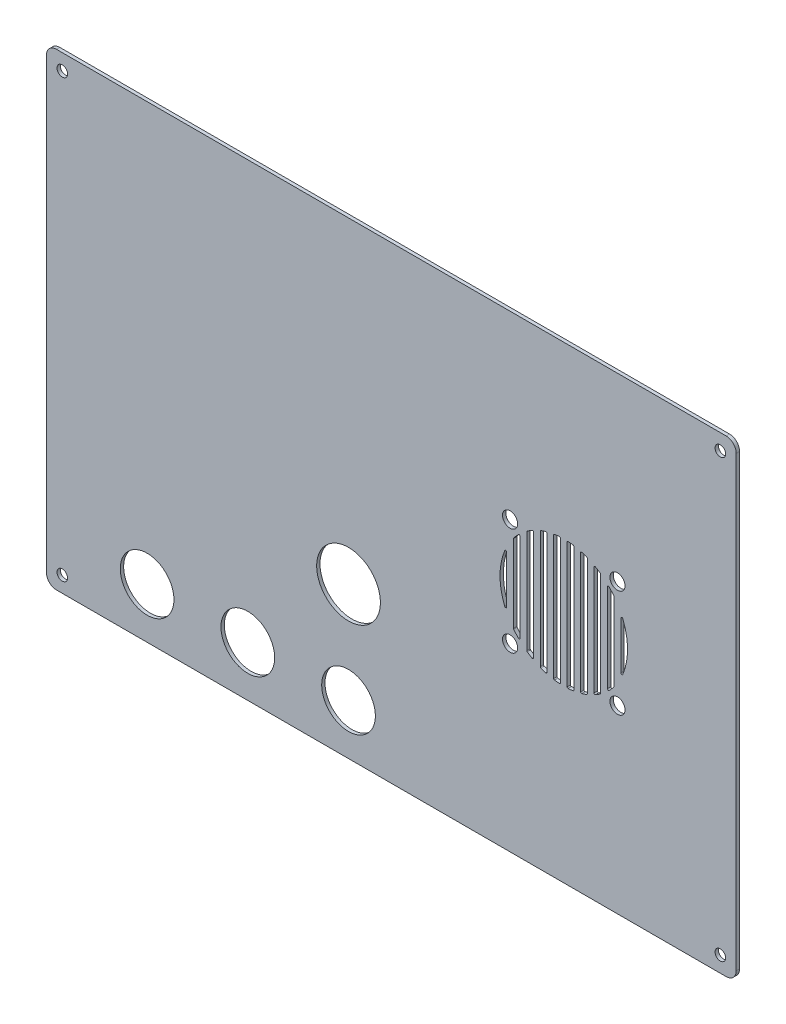
SolidWorks part; units mm, degrees
ref_plane "Спереди" through (0, 0, 0) normal (0, 0, 1) x (1, 0, 0)
ref_plane "Сверху" through (0, 0, 0) normal (0, 1, 0) x (1, 0, 0)
ref_plane "Справа" through (0, 0, 0) normal (1, 0, 0) x (0, 0, -1)
sketch "Эскиз2" plane through (0, 0, 0) normal (0, 0, 1) x (1, 0, 0)
  line L1 (102.75, -69.75) -> (-102.75, -69.75)
  line L2 (102.75, -69.75) -> (102.75, 69.75)
  line L3 (102.75, 69.75) -> (-102.75, 69.75)
  line L4 (-102.75, -69.75) -> (-102.75, 69.75)
  line L5 (102.75, -69.75) -> (-102.75, 69.75) construction
  line L6 (102.75, 69.75) -> (-102.75, -69.75) construction
  point P0 (0, 0)
  dimension "D1" = 205.5
  dimension "D2" = 139.5
base flange "Базовая кромка1" sketch "Эскиз2" thickness 1 reverse thickness direction no parameters "D1"=1.6
fillet "Скругление1" radius 3 4 edges at (-102.75, 69.75, -0.5) (-102.75, -69.75, -0.5) (102.75, -69.75, -0.5) (102.75, 69.75, -0.5)
hole_wizard "Сверло под метчик  спиральное M31" positions "Эскиз4" profile "Эскиз5" hole size "M3x0.5" standard "Ansi Metric"
sketch "Эскиз4" plane through (0, 0, -1) normal (0, 0, -1) x (-1, 0, 0)
  circle A0 centre (-98.0213, -65.0213) radius 1.6 construction
  point P4 (-98.0213, 65.0213)
  point P7 (98.0213, 65.0213)
  point P10 (98.0213, -65.0213)
  point P13 (-98.0213, -65.0213)
sketch "Эскиз5" plane through (98.0213, 65.0213, -1) normal (1, 0, 0) x (0, 1, 0)
  line L0 (0, 0) -> (0, 9.4464)
  line L1 (0, 9.4464) -> (1.575, 8.5)
  line L2 (1.575, 8.5) -> (1.575, 0)
  line L5 (1.575, 0) -> (0, 0)
  line L10 (0, 9.4464) -> (-1.575, 8.5) construction
  line L11 (0, -6.35) -> (0, 107.95) construction
  dimension "Диаметр отверстия" = 3.15
  dimension "Глубина отверстия" = 8.5
  dimension "Угол заточки сверла" = 118
sketch "Эскиз9" plane through (0, 0, -1) normal (0, 0, -1) x (-1, 0, 0)
  line L0 (-102.75, 0) -> (0, 0) construction
  line L1 (-35.375, -16) -> (-67.375, -16) construction
  line L2 (-35.375, -16) -> (-35.375, 16) construction
  line L3 (-35.375, 16) -> (-67.375, 16) construction
  line L4 (-67.375, -16) -> (-67.375, 16) construction
  line L5 (-35.375, -16) -> (-67.375, 16) construction
  line L6 (-35.375, 16) -> (-67.375, -16) construction
  line L7 (-102.75, -66.75) -> (-102.75, 66.75) construction
  circle A0 centre (-51.375, 0) radius 18.5 construction
  circle A1 centre (-67.375, 16) radius 2.25
  circle A2 centre (-35.375, 16) radius 2.25
  circle A3 centre (-35.375, -16) radius 2.25
  circle A4 centre (-67.375, -16) radius 2.25
  point P0 (-51.375, 0)
  point P5 (-51.375, 0)
  dimension "D3" = 4.5
  dimension "D1" = 32
  dimension "D2" = 32
extrude "Вырез-Вытянуть3" cut sketch "Эскиз9" against normal blind 1 normal cut yes
sketch "Эскиз11" plane through (0, 0, -1) normal (0, 0, -1) x (-1, 0, 0)
  line L0 (-68.375, 8.4853) -> (-68.375, -8.4853)
  line L1 (-66.375, 11.6619) -> (-66.375, -11.6619)
  line L2 (-64.375, 13.8564) -> (-64.375, -13.8564)
  line L3 (-52.375, 18.9737) -> (-52.375, -18.9737)
  line L4 (-54.375, 18.7617) -> (-54.375, -18.7617)
  line L5 (-56.375, 18.3303) -> (-56.375, -18.3303)
  line L6 (-58.375, 17.6635) -> (-58.375, -17.6635)
  line L7 (-60.375, 16.7332) -> (-60.375, -16.7332)
  line L8 (-62.375, 15.4919) -> (-62.375, -15.4919)
  line L10 (-51.375, 0) -> (-51.375, 26.4323) construction
  line L11 (-40.375, 15.4919) -> (-40.375, -15.4919)
  line L12 (-42.375, 16.7332) -> (-42.375, -16.7332)
  line L13 (-44.375, 17.6635) -> (-44.375, -17.6635)
  line L14 (-46.375, 18.3303) -> (-46.375, -18.3303)
  line L15 (-48.375, 18.7617) -> (-48.375, -18.7617)
  line L16 (-50.375, 18.9737) -> (-50.375, -18.9737)
  line L17 (-38.375, 13.8564) -> (-38.375, -13.8564)
  line L18 (-36.375, 11.6619) -> (-36.375, -11.6619)
  line L19 (-34.375, 8.4853) -> (-34.375, -8.4853)
  arc A0 (-68.375, 8.4853) -> (-68.375, -8.4853) centre (-51.375, 0) ccw
  arc A1 (-64.375, 13.8564) -> (-66.375, 11.6619) centre (-51.375, 0) ccw
  arc A2 (-60.375, 16.7332) -> (-62.375, 15.4919) centre (-51.375, 0) ccw
  arc A3 (-56.375, 18.3303) -> (-58.375, 17.6635) centre (-51.375, 0) ccw
  arc A4 (-52.375, 18.9737) -> (-54.375, 18.7617) centre (-51.375, 0) ccw
  arc A5 (-66.375, -11.6619) -> (-64.375, -13.8564) centre (-51.375, 0) ccw
  arc A6 (-62.375, -15.4919) -> (-60.375, -16.7332) centre (-51.375, 0) ccw
  arc A7 (-58.375, -17.6635) -> (-56.375, -18.3303) centre (-51.375, 0) ccw
  arc A8 (-54.375, -18.7617) -> (-52.375, -18.9737) centre (-51.375, 0) ccw
  arc A9 (-50.375, -18.9737) -> (-50.375, 18.9737) centre (-51.375, 0) ccw construction
  arc A10 (-48.375, -18.7617) -> (-50.375, -18.9737) centre (-51.375, 0) cw
  arc A11 (-44.375, -17.6635) -> (-46.375, -18.3303) centre (-51.375, 0) cw
  arc A12 (-40.375, -15.4919) -> (-42.375, -16.7332) centre (-51.375, 0) cw
  arc A13 (-36.375, -11.6619) -> (-38.375, -13.8564) centre (-51.375, 0) cw
  arc A14 (-50.375, 18.9737) -> (-48.375, 18.7617) centre (-51.375, 0) cw
  arc A15 (-46.375, 18.3303) -> (-44.375, 17.6635) centre (-51.375, 0) cw
  arc A16 (-42.375, 16.7332) -> (-40.375, 15.4919) centre (-51.375, 0) cw
  arc A17 (-38.375, 13.8564) -> (-36.375, 11.6619) centre (-51.375, 0) cw
  arc A18 (-34.375, 8.4853) -> (-34.375, -8.4853) centre (-51.375, 0) cw
  point P6 (-70.375, 0)
  point P40 (-32.375, 0)
  dimension "D11" = 38
  dimension "D1" = 2
  dimension "D2" = 2
  dimension "D3" = 2
  dimension "D4" = 2
  dimension "D5" = 2
  dimension "D6" = 2
  dimension "D7" = 2
  dimension "D8" = 2
  dimension "D9" = 2
extrude "Вырез-Вытянуть4" cut sketch "Эскиз11" against normal blind 1 normal cut yes
sketch "Эскиз8" plane through (0, 0, -1) normal (0, 0, -1) x (-1, 0, 0)
  line L0 (102.75, 66.75) -> (102.75, -66.75) construction
  line L1 (99.75, -69.75) -> (-99.75, -69.75) construction
  circle A0 centre (42.75, -54.75) radius 8
  circle A1 centre (72.75, -54.75) radius 8
  circle A2 centre (12.75, -54.75) radius 8
  point P8 (48.545, -54.75)
  point P9 (25.98, -56.3889)
  point P10 (47.2914, -54.75)
  point P13 (22.2191, -54.75)
  dimension "D1" = 16
  dimension "D2" = 15
  dimension "D4" = 30
  dimension "D5" = 30
  dimension "D3" = 30
extrude "Вырез-Вытянуть1" cut sketch "Эскиз8" against normal blind 10
sketch "Эскиз10" plane through (0, 0, -1) normal (0, 0, -1) x (-1, 0, 0)
  line L0 (12.75, -54.75) -> (12.75, 5.25) construction
  circle A0 centre (12.75, -24.75) radius 9.5
  point P2 (32.75, -21.2426)
  dimension "D1" = 19
  dimension "D2" = 30
extrude "Вырез-Вытянуть2" cut sketch "Эскиз10" against normal blind 1 normal cut yes
fillet "Скругление2" radius 0.3 36 edges at (50.375, 18.9737, -0.5) (48.375, 18.7617, -0.5) (38.375, 13.8564, -0.5) (36.375, 11.6619, -0.5) (36.375, -11.6619, -0.5) (42.375, 16.7332, -0.5) (40.375, 15.4919, -0.5) (46.375, 18.3303, -0.5) (44.375, 17.6635, -0.5) (52.375, 18.9737, -0.5) (54.375, 18.7617, -0.5) (34.375, 8.4853, -0.5) (34.375, -8.4853, -0.5) (38.375, -13.8564, -0.5) (40.375, -15.4919, -0.5) (42.375, -16.7332, -0.5) (46.375, -18.3303, -0.5) (50.375, -18.9737, -0.5) (44.375, -17.6635, -0.5) (48.375, -18.7617, -0.5) (52.375, -18.9737, -0.5) (54.375, -18.7617, -0.5) (56.375, -18.3303, -0.5) (58.375, -17.6635, -0.5) (56.375, 18.3303, -0.5) (58.375, 17.6635, -0.5) (60.375, 16.7332, -0.5) (62.375, 15.4919, -0.5) (62.375, -15.4919, -0.5) (64.375, -13.8564, -0.5) (66.375, -11.6619, -0.5) (64.375, 13.8564, -0.5) (66.375, 11.6619, -0.5) (68.375, -8.4853, -0.5) (68.375, 8.4853, -0.5) (60.375, -16.7332, -0.5)
sketch "Сгиб-Линии1" plane through (0, 0, 0) normal (0, 1, 0) x (1, 0, 0)
sketch "Граничная рамка1" plane through (0, 0, 0) normal (0, 1, 0) x (1, 0, 0)
sheet metal parameters "Листовой металл3" thickness 1 parameters "D1"=1.6
flat pattern "Развертка3" [suppressed]
sketch "Сгиб-Линии2" plane through (0, 0, 0) normal (0, 1, 0) x (1, 0, 0)
sketch "Граничная рамка2" [suppressed] plane through (0, 0, 0) normal (0, 1, 0) x (1, 0, 0)
sheet metal parameters "Листовой металл4" thickness 1 parameters "D1"=1.6
flat pattern "Развертка3"
sketch "Сгиб-Линии2" plane through (0, 0, 0) normal (0, 1, 0) x (1, 0, 0)
sketch "Граничная рамка2" [suppressed] plane through (0, 0, 0) normal (0, 1, 0) x (1, 0, 0)
sheet metal parameters "Листовой металл5" thickness 1 parameters "D1"=1.6
flat pattern "Развертка3"
sketch "Сгиб-Линии2" plane through (0, 0, 0) normal (0, 1, 0) x (1, 0, 0)
sketch "Граничная рамка2" [suppressed] plane through (0, 0, 0) normal (0, 1, 0) x (1, 0, 0)
sheet metal parameters "Листовой металл6" thickness 1 parameters "D1"=1.6
flat pattern "Развертка3"
sketch "Сгиб-Линии2" plane through (0, 0, 0) normal (0, 1, 0) x (1, 0, 0)
sketch "Граничная рамка2" [suppressed] plane through (0, 0, 0) normal (0, 1, 0) x (1, 0, 0)
sheet metal parameters "Листовой металл7" thickness 1 parameters "D1"=1.6
flat pattern "Развертка3"
sketch "Сгиб-Линии2" plane through (0, 0, 0) normal (0, 1, 0) x (1, 0, 0)
sketch "Граничная рамка2" [suppressed] plane through (0, 0, 0) normal (0, 1, 0) x (1, 0, 0)
sheet metal parameters "Листовой металл8" thickness 1 parameters "D1"=1.6
flat pattern "Развертка3"
sketch "Сгиб-Линии2" plane through (0, 0, 0) normal (0, 1, 0) x (1, 0, 0)
sketch "Граничная рамка2" [suppressed] plane through (0, 0, 0) normal (0, 1, 0) x (1, 0, 0)
equation "\"D2@Эскиз11\"=\"D1@Эскиз11\""
equation "\"D3@Эскиз11\"=\"D1@Эскиз11\""
equation "\"D4@Эскиз11\"=\"D1@Эскиз11\""
equation "\"D5@Эскиз11\"=\"D1@Эскиз11\""
equation "\"D6@Эскиз11\"=\"D1@Эскиз11\""
equation "\"D7@Эскиз11\"=\"D1@Эскиз11\""
equation "\"D8@Эскиз11\"=\"D1@Эскиз11\""
equation "\"D9@Эскиз11\"=\"D1@Эскиз11\""
